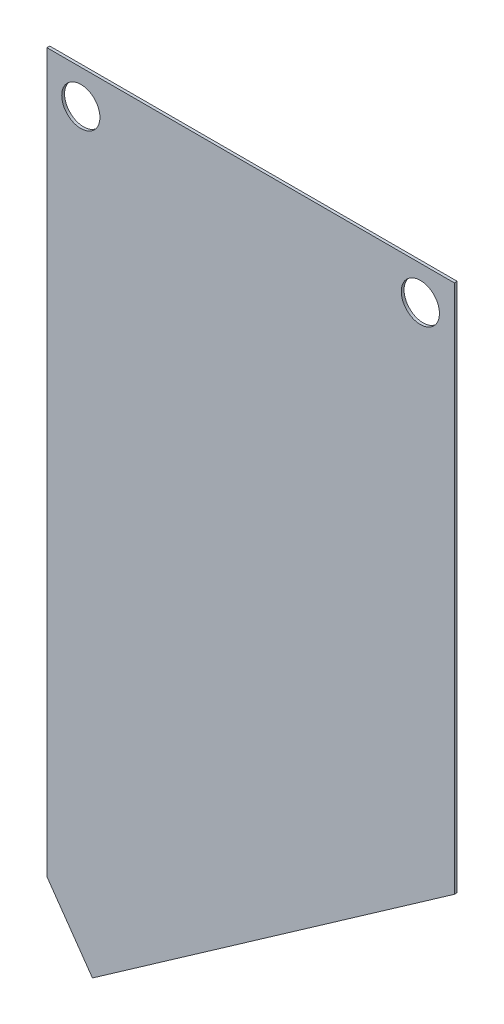
SolidWorks part; units mm, degrees
material "Acrylic (Medium-high impact)"
ref_plane "Front Plane" through (0, 0, 0) normal (0, 0, 1) x (1, 0, 0)
ref_plane "Top Plane" through (0, 0, 0) normal (0, 1, 0) x (1, 0, 0)
ref_plane "Right Plane" through (0, 0, 0) normal (1, 0, 0) x (0, 0, -1)
sketch "Sketch1" plane through (0, 0, 0) normal (0, 0, 1) x (1, 0, 0)
  line L1 (-50.8, 0) -> (254, 0)
  line L2 (-50.8, 0) -> (-50.8, -609.6)
  line L3 (-50.8, -609.6) -> (254, -609.6)
  line L4 (254, 0) -> (254, -609.6)
extrude "Boss-Extrude1" add sketch "Sketch1" along normal blind 2.1082
sketch "Sketch2" plane through (0, 0, 2.1082) normal (0, 0, 1) x (1, 0, 0)
  line L0 (-50.8, -537.0501) -> (-16.7127, -585.7318)
  line L2 (-16.7127, -585.7318) -> (255.7234, -394.97)
  line L4 (255.7234, -394.97) -> (255.7234, -609.6)
  line L5 (255.7234, -609.6) -> (-50.8, -609.6)
  line L8 (-50.8, -609.6) -> (-50.8, -537.0501)
extrude "Cut-Extrude1" cut sketch "Sketch2" against normal blind 2.1082
sketch "Sketch3" plane through (0, 0, 0) normal (0, 0, -1) x (-1, 0, 0)
  circle A1 centre (25.4, -25.4) radius 14.2875
extrude "Cut-Extrude2" cut sketch "Sketch3" against normal blind 2.1082
sketch "Sketch4" plane through (0, 0, 0) normal (0, 0, -1) x (-1, 0, 0)
  circle A0 centre (-228.6, -25.4) radius 14.2875
extrude "Cut-Extrude3" cut sketch "Sketch4" against normal blind 2.1082
